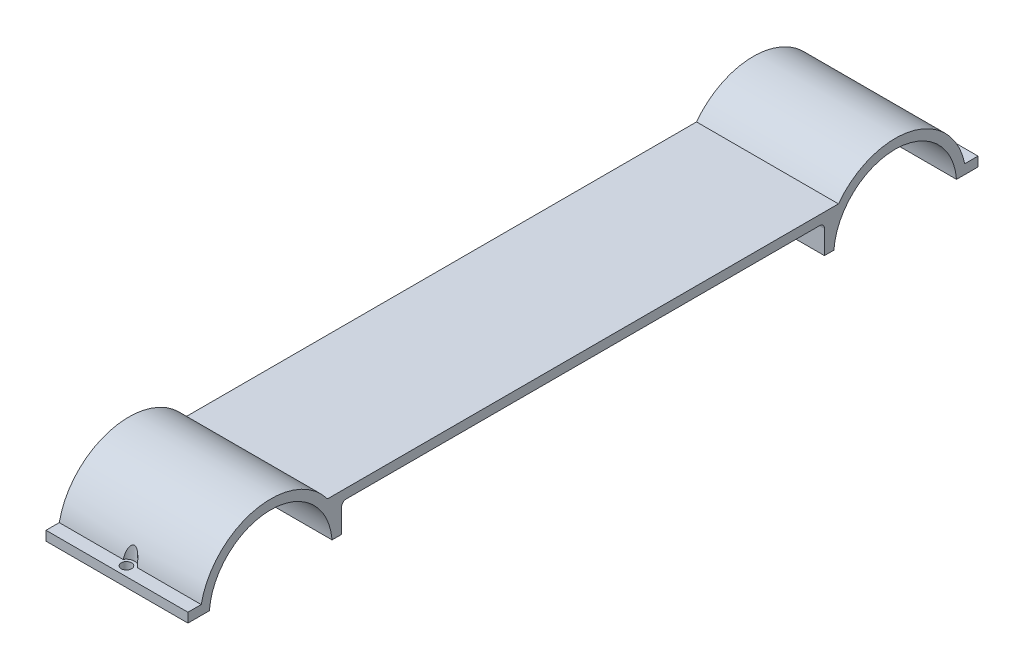
SolidWorks part; units mm, degrees
ref_plane "Спереди" through (0, 0, 0) normal (0, 0, 1) x (1, 0, 0)
ref_plane "Сверху" through (0, 0, 0) normal (0, 1, 0) x (1, 0, 0)
ref_plane "Справа" through (0, 0, 0) normal (1, 0, 0) x (0, 0, -1)
sketch "Эскиз1" plane through (0, 0, 0) normal (1, 0, 0) x (0, 0, -1)
  line L0 (-83.5, 0) -> (83.5, 0) construction
  line L1 (-83.5, 3) -> (-83.5, 1)
  line L2 (-83.5, 1) -> (-78.9615, 1)
  line L3 (-51.0385, 7) -> (-51.0385, 1)
  line L4 (78.9615, 1) -> (83.5, 1)
  line L5 (83.5, 1) -> (83.5, 3)
  line L6 (-83.5, 3) -> (-80.6969, 3)
  line L7 (-51.0385, 1) -> (-53.0385, 1)
  line L8 (80.6969, 3) -> (83.5, 3)
  line L9 (66, 13.2) -> (-66, 13) construction
  line L10 (-83.5, 1) -> (72.9784, 1) construction
  line L11 (-51.0385, 7) -> (51.0385, 7)
  line L12 (51.0385, 7) -> (51.0385, 1)
  line L13 (-54, 9) -> (54, 9)
  line L14 (51.0385, 1) -> (53.0385, 1)
  arc A0 (-78.9615, 1) -> (-53.0385, 1) centre (-66, 0) cw
  arc A1 (78.9615, 1) -> (53.0385, 1) centre (66, 0) ccw
  arc A2 (-80.6969, 3) -> (-54, 9) centre (-66, 0) cw
  arc A3 (80.6969, 3) -> (54, 9) centre (66, 0) ccw
  dimension "D5" = 1
  dimension "D6" = 1
  dimension "D9" = 2
  dimension "D10" = 2
  dimension "D13" = 2
  dimension "D14" = 13
  dimension "D15" = 13
  dimension "D2" = 15
  dimension "D16" = 15
  dimension "D1" = 167
  dimension "D3" = 17.5
  dimension "D4" = 17.5
  dimension "D7" = 2
  dimension "3" = 3
  dimension "D8" = 3
  dimension "D11" = 25.923
  dimension "D12" = 25.923
  dimension "D17" = 108
  dimension "D18" = 83.5
extrude "Бобышка-Вытянуть1" add sketch "Эскиз1" along normal blind 15 and the other way blind 15
fillet "Скругление4" radius 1 2 edges at (0, 7, -51.0385) (0, 7, 51.0385)
sketch "Эскиз2" plane through (0, 3, 0) normal (0, 1, 0) x (1, 0, 0)
  line L1 (-15, 83.5) -> (15, 83.5) construction
  circle A0 centre (0, 81.5) radius 1.1
  dimension "D2" = 2.2
  dimension "D1" = 2
extrude "Вырез-Вытянуть1" cut sketch "Эскиз2" against normal blind 10 and the other way blind 10
sketch "Эскиз3" plane through (0, 3, 0) normal (0, 1, 0) x (1, 0, 0)
  line L0 (-15, 80.6969) -> (-0.7517, 80.6969) construction
  line L1 (-15, 78.9615) -> (15, 78.9615) construction
  line L2 (-15, 83.5) -> (-15, 80.6969) construction
  circle A0 centre (0, 81.5) radius 1.7035
  point P9 (-15, 82.0985)
  dimension "D1" = 0.8031
  dimension "D2" = 2.5385
  dimension "D3" = 15
extrude "Вырез-Вытянуть2" cut sketch "Эскиз3" along normal blind 10
mirror "Зеркальное отражение1" about plane through (0, 0, 0) normal (0, 0, 1) of "Вырез-Вытянуть2", "Вырез-Вытянуть1"
